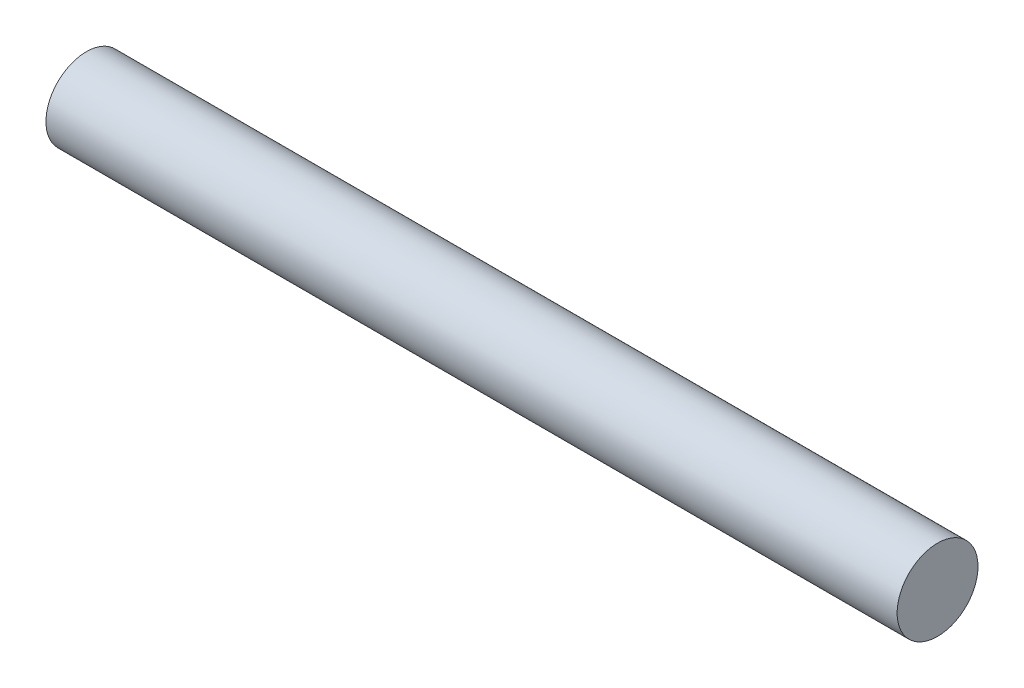
SolidWorks part; units mm, degrees
ref_plane "Alzado" through (0, 0, 0) normal (0, 0, 1) x (1, 0, 0)
ref_plane "Planta" through (0, 0, 0) normal (0, 1, 0) x (1, 0, 0)
ref_plane "Vista lateral" through (0, 0, 0) normal (1, 0, 0) x (0, 0, -1)
sketch "Croquis1" plane through (0, 0, 0) normal (1, 0, 0) x (0, 0, -1)
  circle A0 centre (0, 0) radius 9.5
  dimension "D1" = 19
extrude "Saliente-Extruir1" add sketch "Croquis1" along normal blind 200
